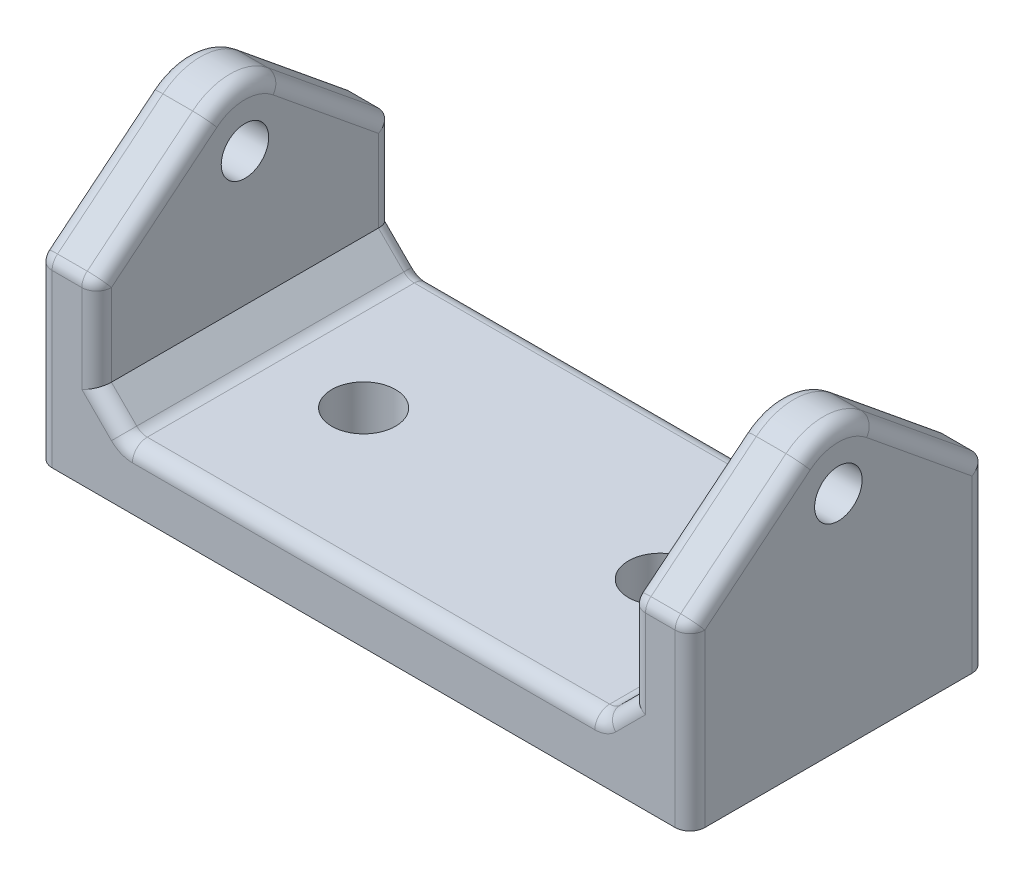
SolidWorks part; units mm, degrees
ref_plane "Front Plane" through (0, 0, 0) normal (0, 0, 1) x (1, 0, 0)
ref_plane "Top Plane" through (0, 0, 0) normal (0, 1, 0) x (1, 0, 0)
ref_plane "Right Plane" through (0, 0, 0) normal (1, 0, 0) x (0, 0, -1)
sketch "Sketch1" plane through (0, 0, 0) normal (1, 0, 0) x (0, 0, -1)
  line L0 (-10, 6) -> (-2.5296, 12.0986)
  line L1 (-10, -6) -> (10, -6)
  line L2 (-10, -6) -> (-10, 6)
  line L3 (-10, 6) -> (10, 6)
  line L4 (10, -6) -> (10, 6)
  line L5 (-10, -6) -> (10, 6) construction
  line L6 (-10, 6) -> (10, -6) construction
  line L7 (10, 6) -> (2.5296, 12.0986)
  line L8 (0, 9) -> (0, 6) construction
  arc A0 (-2.5296, 12.0986) -> (2.5296, 12.0986) centre (0, 9) cw
  circle A1 centre (0, 9) radius 1.6
  point P0 (0, 0)
  dimension "D2" = 3.2
  dimension "D4" = 4
  dimension "D1" = 12
  dimension "D3" = 20
  dimension "D5" = 3
extrude "Boss-Extrude1" add sketch "Sketch1" along normal blind 44 contours L1 L4 L3 L2 | A0 L0 L3 L7 A1 region at (0, 0, 0) region at (0, 8.8851, 6.1308)
sketch "Sketch2" plane through (0, 0, 10) normal (0, 0, 1) x (1, 0, 0)
  line L0 (44, 13) -> (0, 13) construction
  line L1 (4, -2) -> (40, -2)
  line L2 (4, -2) -> (4, 13)
  line L3 (4, 13) -> (40, 13)
  line L4 (40, -2) -> (40, 13)
  line L5 (0, 13) -> (4, 13) construction
  line L6 (40, 13) -> (44, 13) construction
  line L7 (44, -6) -> (0, -6) construction
  dimension "D1" = 4
  dimension "D2" = 4
extrude "Cut-Extrude1" cut sketch "Sketch2" against normal through all
chamfer "Chamfer1" distance 2 angle 45 2 edges at (40, -2, 0) (4, -2, 0)
fillet "Fillet1" radius 1 30 edges at (40, 3, -10) (40, 3, 10) (4, 3, -10) (4, 3, 10) (0, 0, -10) (44, 0, -10) (44, 0, 10) (0, 0, 10) (44, 9.0493, -6.2648) (44, 13, 0) (40, 9.0493, -6.2648) (40, 13, 0) (0, 9.0493, -6.2648) (0, 13, 0) (4, 9.0493, -6.2648) (4, 13, 0) (44, 9.0493, 6.2648) (42, 6, 10) (40, 9.0493, 6.2648) (2, 6, 10) (0, 9.0493, 6.2648) (4, 9.0493, 6.2648) (5, -1, -10) (5, -1, 10) (39, -1, -10) (39, -1, 10) (6, -2, 0) (22, -2, -10) (38, -2, 0) (22, -2, 10)
sketch "Sketch3" plane through (0, -2, 0) normal (0, 1, 0) x (1, 0, 0)
  line L0 (22, 10) -> (22, -10) construction
  line L1 (6.4142, 10) -> (37.5858, 10) construction
  line L2 (37.5858, -10) -> (6.4142, -10) construction
  line L3 (12, 0) -> (32, 0)
  circle A0 centre (12, 0) radius 2.15
  circle A1 centre (32, 0) radius 2.15
  point P14 (22, 0)
  dimension "D1" = 4.3
  dimension "D2" = 20
extrude "Cut-Extrude2" cut sketch "Sketch3" against normal through all contours A0 | A1 region at (32, -2, -2.0892) region at (9.9108, -2, 0)
